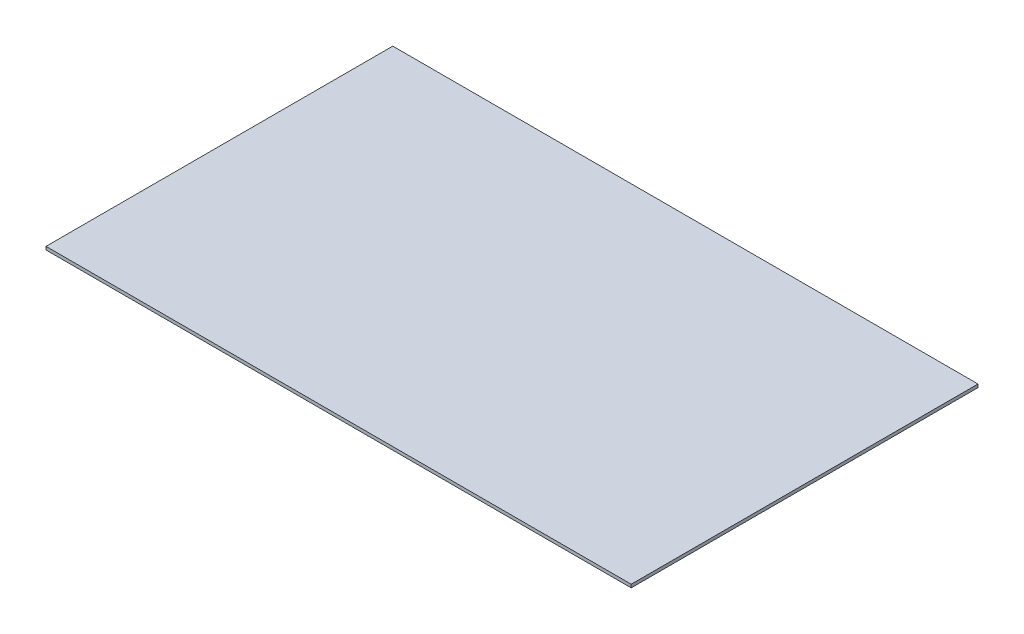
SolidWorks part; units mm, degrees
ref_plane "Front Plane" through (0, 0, 0) normal (0, 0, 1) x (1, 0, 0)
ref_plane "Top Plane" through (0, 0, 0) normal (0, 1, 0) x (1, 0, 0)
ref_plane "Right Plane" through (0, 0, 0) normal (1, 0, 0) x (0, 0, -1)
sketch "Sketch1" plane through (0, 0, 0) normal (0, 1, 0) x (1, 0, 0)
  line L1 (0, 0) -> (514.35, 0)
  line L2 (0, 0) -> (0, 304.8)
  line L3 (0, 304.8) -> (514.35, 304.8)
  line L4 (514.35, 0) -> (514.35, 304.8)
  dimension "D1" = 514.35
  dimension "D2" = 304.8
extrude "Boss-Extrude1" add sketch "Sketch1" along normal blind 2.794
sketch "Sketch3" plane through (0, 2.794, 0) normal (0, 1, 0) x (1, 0, 0)
  line L0 (152.4, 342.4398) -> (152.4, -37.6398) construction
  line L1 (0, 304.8) -> (0, 0) construction
  line L4 (514.35, 304.8) -> (0, 304.8) construction
  line L5 (152.4, 304.8) -> (76.2, 284.3823) construction
  line L6 (76.2, 284.3823) -> (20.4177, 228.6) construction
  line L7 (20.4177, 228.6) -> (0, 152.4) construction
  line L8 (0, 152.4) -> (20.4177, 76.2) construction
  line L9 (20.4177, 76.2) -> (76.2, 20.4177) construction
  line L10 (76.2, 20.4177) -> (152.4, 0) construction
  line L11 (152.4, 0) -> (228.6, 20.4177) construction
  line L12 (228.6, 20.4177) -> (284.3823, 76.2) construction
  line L13 (284.3823, 76.2) -> (304.8, 152.4) construction
  line L14 (304.8, 152.4) -> (284.3823, 228.6) construction
  line L15 (284.3823, 228.6) -> (228.6, 284.3823) construction
  line L16 (228.6, 284.3823) -> (152.4, 304.8) construction
  circle A0 centre (152.4, 152.4) radius 147.2071 construction
  point P9 (0, 0)
  point P23 (0, 0)
  dimension "D1" = 152.4
  dimension "D3" = 304.8
